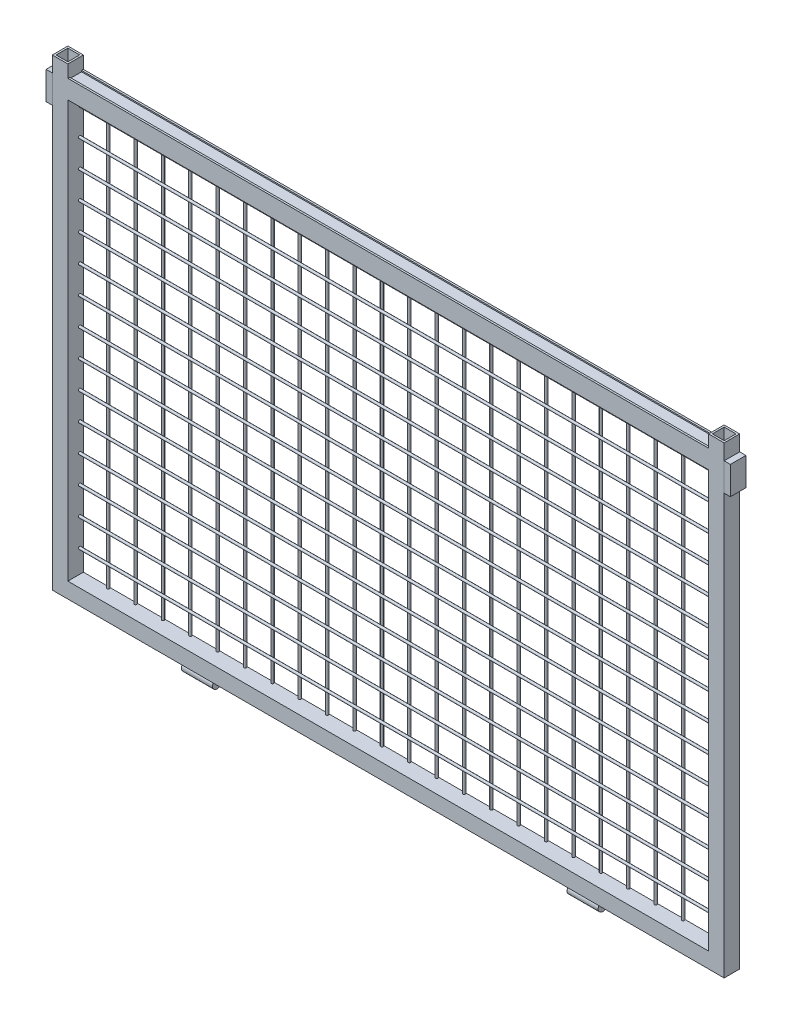
SolidWorks part; units mm, degrees
ref_plane "Piano frontale" through (0, 0, 0) normal (0, 0, 1) x (1, 0, 0)
ref_plane "Piano superiore" through (0, 0, 0) normal (0, 1, 0) x (1, 0, 0)
ref_plane "Piano destro" through (0, 0, 0) normal (1, 0, 0) x (0, 0, -1)
sketch "Schizzo1" plane through (0, 0, 0) normal (0, 1, 0) x (1, 0, 0)
  line L0 (-537, 9.5) -> (-518, 9.5)
  line L1 (-540, -12.5) -> (-515, -12.5)
  line L2 (-540, -12.5) -> (-540, 12.5)
  line L3 (-540, 12.5) -> (-515, 12.5)
  line L4 (-515, -12.5) -> (-515, 12.5)
  line L5 (-518, -9.5) -> (-518, 9.5)
  line L6 (-537, -9.5) -> (-518, -9.5)
  line L7 (-537, -9.5) -> (-537, 9.5)
  line L8 (0, 0) -> (0, 211.96) construction
  line L9 (537, -9.5) -> (537, 9.5)
  line L10 (537, -9.5) -> (518, -9.5)
  line L11 (518, -9.5) -> (518, 9.5)
  line L12 (515, -12.5) -> (515, 12.5)
  line L13 (540, 12.5) -> (515, 12.5)
  line L14 (540, -12.5) -> (540, 12.5)
  line L15 (540, -12.5) -> (515, -12.5)
  line L16 (537, 9.5) -> (518, 9.5)
  point P4 (-515, 0)
  dimension "D1" = 25
  dimension "D2" = 25
  dimension "D3" = 540
  dimension "D4" = 3
extrude "Estrusione-Estrusione1" add sketch "Schizzo1" along normal blind 745
sketch "Schizzo2" plane through (-515, 0, 0) normal (1, 0, 0) x (0, 0, -1)
  line L0 (12.5, 745) -> (12.5, 0) construction
  line L1 (-12.5, 0) -> (12.5, 0)
  line L2 (-12.5, 0) -> (-12.5, 25)
  line L3 (-12.5, 25) -> (12.5, 25)
  line L4 (12.5, 0) -> (12.5, 25)
  line L5 (-9.5, 22) -> (9.5, 22)
  line L6 (9.5, 3) -> (9.5, 22)
  line L7 (-9.5, 3) -> (9.5, 3)
  line L8 (-9.5, 3) -> (-9.5, 22)
  line L9 (-12.5, 372.5) -> (12.5, 372.5) construction
  line L10 (-12.5, 745) -> (-12.5, 0) construction
  line L11 (-9.5, 742) -> (-9.5, 723)
  line L12 (-9.5, 742) -> (9.5, 742)
  line L13 (9.5, 742) -> (9.5, 723)
  line L14 (-9.5, 723) -> (9.5, 723)
  line L15 (12.5, 745) -> (12.5, 720)
  line L16 (-12.5, 720) -> (12.5, 720)
  line L17 (-12.5, 745) -> (-12.5, 720)
  line L18 (-12.5, 745) -> (12.5, 745)
  dimension "D1" = 25
  dimension "D2" = 3
extrude "Estrusione-Estrusione2" add sketch "Schizzo2" along normal up to next separate body
ref_plane "Piano1" through (335, 0, 0) normal (1, 0, 0) x (0, 0, -1)
sketch "Schizzo4" plane through (335, 0, 0) normal (1, 0, 0) x (0, 0, -1)
  line L0 (-12.5, 745) -> (-12.5, 0) construction
  line L1 (-12.5, 0) -> (12.5, 0) construction
  circle A0 centre (-2.5, -7.5) radius 7.5
  dimension "D1" = 15
  dimension "D2" = 10
extrude "Estrusione-Estrusione3" add sketch "Schizzo4" against normal blind 50 separate body
mirror "Specchia1" about plane through (0, 0, 0) normal (1, 0, 0) of bodies 105
sketch "Schizzo5" plane through (540, 0, 0) normal (1, 0, 0) x (0, 0, -1)
  line L0 (-12.5, 745) -> (-12.5, 0) construction
  line L1 (-12.5, 720) -> (12.5, 720)
  line L2 (-12.5, 720) -> (-12.5, 675)
  line L3 (-12.5, 675) -> (12.5, 675)
  line L4 (12.5, 720) -> (12.5, 675)
  line L5 (12.5, 745) -> (12.5, 0) construction
  line L6 (-12.5, 745) -> (12.5, 745) construction
  dimension "D1" = 25
  dimension "D2" = 45
extrude "Estrusione-Estrusione4" add sketch "Schizzo5" along normal blind 10 separate body
mirror "Specchia2" about plane through (0, 0, 0) normal (1, 0, 0) of bodies 107
sketch "Schizzo6" plane through (0, 25, 0) normal (0, 1, 0) x (1, 0, 0)
  line L0 (-515, 12.5) -> (-515, -12.5) construction
  line L1 (515, 12.5) -> (-515, 12.5) construction
  line L2 (-473, 10.5) -> (-429, 10.5) construction
  circle A0 centre (-473, 10.5) radius 2
  circle A1 centre (-429, 10.5) radius 2
  circle A2 centre (-385, 10.5) radius 2
  circle A3 centre (-341, 10.5) radius 2
  circle A4 centre (-297, 10.5) radius 2
  circle A5 centre (-253, 10.5) radius 2
  circle A6 centre (-209, 10.5) radius 2
  circle A7 centre (-165, 10.5) radius 2
  circle A8 centre (-121, 10.5) radius 2
  circle A9 centre (-77, 10.5) radius 2
  circle A10 centre (-33, 10.5) radius 2
  circle A11 centre (11, 10.5) radius 2
  circle A12 centre (55, 10.5) radius 2
  circle A13 centre (99, 10.5) radius 2
  circle A14 centre (143, 10.5) radius 2
  circle A15 centre (187, 10.5) radius 2
  circle A16 centre (231, 10.5) radius 2
  circle A17 centre (275, 10.5) radius 2
  circle A18 centre (319, 10.5) radius 2
  circle A19 centre (363, 10.5) radius 2
  circle A20 centre (407, 10.5) radius 2
  circle A21 centre (451, 10.5) radius 2
  circle A22 centre (495, 10.5) radius 2
  dimension "D1" = 4
  dimension "D2" = 42
  dimension "D4" = 44
  dimension "D3" = 23
extrude "Estrusione-Estrusione5" add sketch "Schizzo6" along normal up to next
sketch "Schizzo7" plane through (-515, 0, 0) normal (1, 0, 0) x (0, 0, -1)
  line L1 (8.5, 720) -> (8.5, 25) construction
  line L2 (6.5, 678) -> (6.5, 634) construction
  line L3 (12.5, 720) -> (-12.5, 720) construction
  circle A0 centre (6.5, 678) radius 2
  circle A1 centre (6.5, 634) radius 2
  circle A2 centre (6.5, 590) radius 2
  circle A3 centre (6.5, 546) radius 2
  circle A4 centre (6.5, 502) radius 2
  circle A5 centre (6.5, 458) radius 2
  circle A6 centre (6.5, 414) radius 2
  circle A7 centre (6.5, 370) radius 2
  circle A8 centre (6.5, 326) radius 2
  circle A9 centre (6.5, 282) radius 2
  circle A10 centre (6.5, 238) radius 2
  circle A11 centre (6.5, 194) radius 2
  circle A12 centre (6.5, 150) radius 2
  circle A13 centre (6.5, 106) radius 2
  circle A14 centre (6.5, 62) radius 2
  dimension "D1" = 4
  dimension "D2" = 42
  dimension "D4" = 44
  dimension "D3" = 15
extrude "Estrusione-Estrusione7" add sketch "Schizzo7" along normal up to next separate body
sketch "Schizzo8" plane through (0, 0, -12.5) normal (0, 0, -1) x (-1, 0, 0)
  line L0 (515, 745) -> (515, 0) construction
  line L1 (-515, 745) -> (515, 745)
  line L2 (-515, 745) -> (-515, 725)
  line L3 (-515, 725) -> (515, 725)
  line L4 (515, 745) -> (515, 725)
  dimension "D1" = 20
extrude "Taglio-Estrusione1" cut sketch "Schizzo8" against normal blind 39
sketch "Schizzo9" plane through (515, 0, 0) normal (-1, 0, 0) x (0, 0, 1)
  line L0 (-12.5, 745) -> (-12.5, 0) construction
  line L1 (12.5, 720) -> (-12.5, 720)
  line L2 (12.5, 720) -> (12.5, 695)
  line L3 (12.5, 695) -> (-12.5, 695)
  line L4 (-12.5, 720) -> (-12.5, 695)
  dimension "D1" = 25
extrude "Estrusione-Estrusione8" add sketch "Schizzo9" along normal up to next
